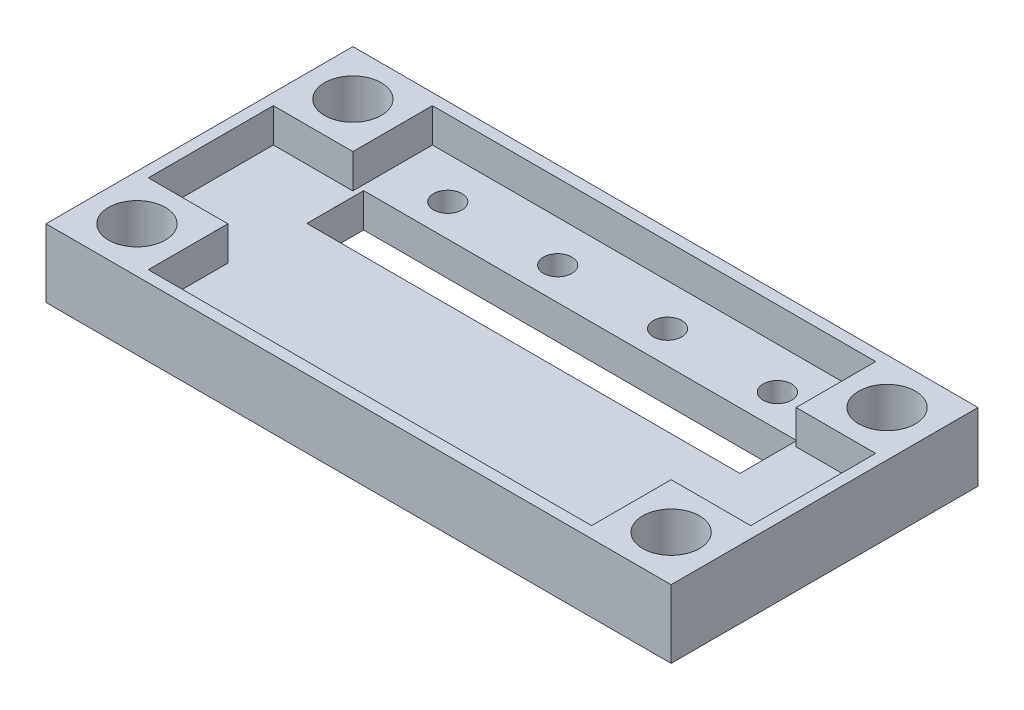
SolidWorks part; units mm, degrees
ref_plane "Front Plane" through (0, 0, 0) normal (0, 0, 1) x (1, 0, 0)
ref_plane "Top Plane" through (0, 0, 0) normal (0, 1, 0) x (1, 0, 0)
ref_plane "Right Plane" through (0, 0, 0) normal (1, 0, 0) x (0, 0, -1)
sketch "Sketch1" plane through (0, 0, 0) normal (0, 1, 0) x (1, 0, 0)
  line L9 (27.5, -13.5) -> (-27.5, -13.5)
  line L10 (27.5, -13.5) -> (27.5, 13.5)
  line L11 (27.5, 13.5) -> (-27.5, 13.5)
  line L20 (-27.5, -13.5) -> (-27.5, 13.5)
  line L21 (27.5, -13.5) -> (-27.5, 13.5) construction
  line L22 (27.5, 13.5) -> (-27.5, -13.5) construction
  line L23 (-19.05, 6) -> (19.05, 6)
  line L24 (-19.05, 6) -> (-19.05, 1)
  line L25 (-19.05, 1) -> (19.05, 1)
  line L26 (19.05, 6) -> (19.05, 1)
  point P0 (0, 0)
  point P10 (0, 6)
  point P11 (0, 13.5)
  dimension "D2" = 55
  dimension "D1" = 27
  dimension "D3" = 38.1
  dimension "D4" = 7.5
  dimension "D5" = 5
extrude "Bottom Base" add sketch "Sketch1" along normal blind 3
sketch "Sketch3" plane through (0, 3, 0) normal (0, 1, 0) x (1, 0, 0)
  line L0 (-27.5, 8.85) -> (27.5, 8.85) construction
  line L1 (-27.5, 13.5) -> (-27.5, -13.5) construction
  line L2 (27.5, -13.5) -> (27.5, 13.5) construction
  line L3 (-14.5, 10.1) -> (14.5, 10.1) construction
  line L4 (19.05, 6) -> (-19.05, 6) construction
  circle A0 centre (-14.5, 8.85) radius 1.09 construction
  circle A1 centre (-14.5, 8.85) radius 1.09 construction
  circle A2 centre (-14.5, 8.85) radius 1.25
  circle A3 centre (14.5, 8.85) radius 1.25
  circle A4 centre (-4.83, 8.85) radius 1.25
  circle A5 centre (4.84, 8.85) radius 1.25
  point P21 (0, 6)
  point P22 (0, 10.1)
  dimension "D2" = 2.5
  dimension "D1" = 29
  dimension "D3" = 9.67
  dimension "D4" = 9.67
extrude "Sensor Mounting Holes" cut sketch "Sketch3" against normal blind 3
sketch "Sketch4" plane through (0, 3, 0) normal (0, 1, 0) x (1, 0, 0)
  line L0 (27.5, -13.5) -> (27.5, 13.5) construction
  line L1 (27.5, 13.5) -> (-27.5, 13.5) construction
  line L2 (-27.5, -13.5) -> (27.5, -13.5) construction
  line L3 (-27.5, 13.5) -> (-27.5, -13.5) construction
  line L4 (27.5, -13.5) -> (27.5, 13.5)
  line L5 (27.5, 13.5) -> (-27.5, 13.5)
  line L6 (-27.5, -13.5) -> (27.5, -13.5)
  line L7 (-27.5, 13.5) -> (-27.5, -13.5)
  line L8 (26.5, -12.5) -> (26.5, 12.5)
  line L9 (26.5, 12.5) -> (-26.5, 12.5)
  line L10 (-26.5, 12.5) -> (-26.5, -12.5)
  line L11 (-26.5, -12.5) -> (26.5, -12.5)
  line L12 (0, -13.5) -> (0, 13.5) construction
  line L13 (-26.5, -12.5) -> (-19.5, -12.5)
  line L14 (-26.5, -12.5) -> (-26.5, -5.5)
  line L15 (-26.5, -5.5) -> (-19.5, -5.5)
  line L16 (-19.5, -12.5) -> (-19.5, -5.5)
  line L29 (27.5, 0) -> (-27.5, 0) construction
  line L30 (26.5, -5.5) -> (19.5, -5.5)
  line L31 (19.5, -12.5) -> (19.5, -5.5)
  line L32 (26.5, -12.5) -> (19.5, -12.5)
  line L33 (26.5, -12.5) -> (26.5, -5.5)
  line L34 (26.5, 12.5) -> (19.5, 12.5)
  line L35 (19.5, 12.5) -> (19.5, 5.5)
  line L36 (26.5, 5.5) -> (19.5, 5.5)
  line L37 (26.5, 12.5) -> (26.5, 5.5)
  line L38 (-26.5, 5.5) -> (-19.5, 5.5)
  line L39 (-19.5, 12.5) -> (-19.5, 5.5)
  line L40 (-26.5, 12.5) -> (-19.5, 12.5)
  line L41 (-26.5, 12.5) -> (-26.5, 5.5)
  point P14 (0, 0)
  point P17 (0, 0)
  line M13 (-27.5, 13.5) -> (-27.5, -13.5)
  line M14 (-27.5, -13.5) -> (27.5, -13.5)
  line M15 (27.5, -13.5) -> (27.5, 13.5)
  line M16 (27.5, 13.5) -> (-27.5, 13.5)
  dimension "D2" = 7
  dimension "D1" = 1
extrude "Outer Rim" add sketch "Sketch4" along normal blind 3 contours L39 L9 L10 L38 | L11 L16 L15 L10 | L31 L11 L8 L30 | L36 L8 L9 L35 | L11 L10 L9 L8 M16 M13 M14 M15 region at (0, 3, 12.8873) region at (23, 3, 9) region at (23, 3, -9) region at (-23, 3, 9) region at (-23, 3, -9)
sketch "Sketch6" plane through (0, 6, 0) normal (0, 1, 0) x (1, 0, 0)
  line L0 (-26.5, -5.5) -> (-19.5, -5.5) construction
  line L1 (-19.5, 5.5) -> (-27.5, 5.5) construction
  line L2 (-19.5, 5.5) -> (-19.5, 13.5) construction
  line L3 (-19.5, 13.5) -> (-27.5, 13.5) construction
  line L4 (-27.5, 5.5) -> (-27.5, 13.5) construction
  line L5 (-19.5, 5.5) -> (-27.5, 13.5) construction
  line L6 (-19.5, 13.5) -> (-27.5, 5.5) construction
  line L7 (-19.5, -13.5) -> (-27.5, -13.5) construction
  line L8 (-19.5, -13.5) -> (-19.5, -5.5) construction
  line L9 (-19.5, -5.5) -> (-27.5, -5.5) construction
  line L10 (-27.5, -13.5) -> (-27.5, -5.5) construction
  line L11 (-19.5, -13.5) -> (-27.5, -5.5) construction
  line L12 (-19.5, -5.5) -> (-27.5, -13.5) construction
  line L17 (-26.5, -5.5) -> (-19.5, -5.5) construction
  line L18 (19.5, -12.5) -> (19.5, -5.5) construction
  line L23 (27.5, 5.5) -> (19.5, 5.5) construction
  line L24 (27.5, 5.5) -> (27.5, 13.5) construction
  line L25 (27.5, 13.5) -> (19.5, 13.5) construction
  line L26 (19.5, 5.5) -> (19.5, 13.5) construction
  line L27 (27.5, 5.5) -> (19.5, 13.5) construction
  line L28 (27.5, 13.5) -> (19.5, 5.5) construction
  line L29 (27.5, -13.5) -> (19.5, -13.5) construction
  line L30 (27.5, -13.5) -> (27.5, -5.5) construction
  line L31 (27.5, -5.5) -> (19.5, -5.5) construction
  line L32 (19.5, -13.5) -> (19.5, -5.5) construction
  line L33 (27.5, -13.5) -> (19.5, -5.5) construction
  line L34 (27.5, -5.5) -> (19.5, -13.5) construction
  line L35 (-19.5, -12.5) -> (-19.5, -5.5) construction
  line L36 (-19.5, -12.5) -> (-19.5, -5.5) construction
  line L37 (27.5, -13.5) -> (27.5, 13.5) construction
  point P0 (-23.5, 9.5)
  point P5 (-23.5, -9.5)
  point P10 (23.5, -9.5)
  point P16 (23.5, 9.5)
  point P27 (19.4, 7.5)
  point P29 (25.4, 13.5)
  point P31 (19.4, -7.5)
  point P34 (25.4, -13.5)
  point P36 (-19.4, -7.5)
  point P41 (25.4, -8.2139)
  point P44 (19.4, -7.5)
hole_wizard "M4 bolt holes" positions "Sketch7" profile "Sketch8" hole size "Ø5.0" standard "ANSI Metric" end condition through all
sketch "Sketch7" plane through (0, 6, 0) normal (0, 1, 0) x (1, 0, 0)
  line L0 (-19.5, -13.5) -> (-27.5, -5.5) construction
  point P0 (-23.5, 9.5)
  point P3 (-23.5, -9.5)
  point P7 (23.5, 9.5)
  point P10 (23.5, -9.5)
sketch "Sketch8" plane through (-23.5, 6, -9.5) normal (1, 0, 0) x (0, 0, 1)
  line L0 (0, 0) -> (0, 6)
  line L1 (0, 6) -> (2.5, 6)
  line L2 (2.5, 6) -> (2.5, 0)
  line L5 (2.5, 0) -> (0, 0)
  line L11 (0, -6.35) -> (0, 107.95) construction
  dimension "Thru Hole Dia." = 5
  dimension "Thru Hole Depth" = 6
sketch "Sketch10" plane through (0, 0, 0) normal (0, -1, 0) x (1, 0, 0)
  line L0 (-27.5, -3.5) -> (27.5, -3.5) construction
  line L1 (-27.5, -13.5) -> (-27.5, 13.5) construction
  line L2 (27.5, 13.5) -> (27.5, -13.5) construction
  line L3 (-19.05, -6) -> (-19.05, -1) construction
  point P8 (-19.05, -3.5)
